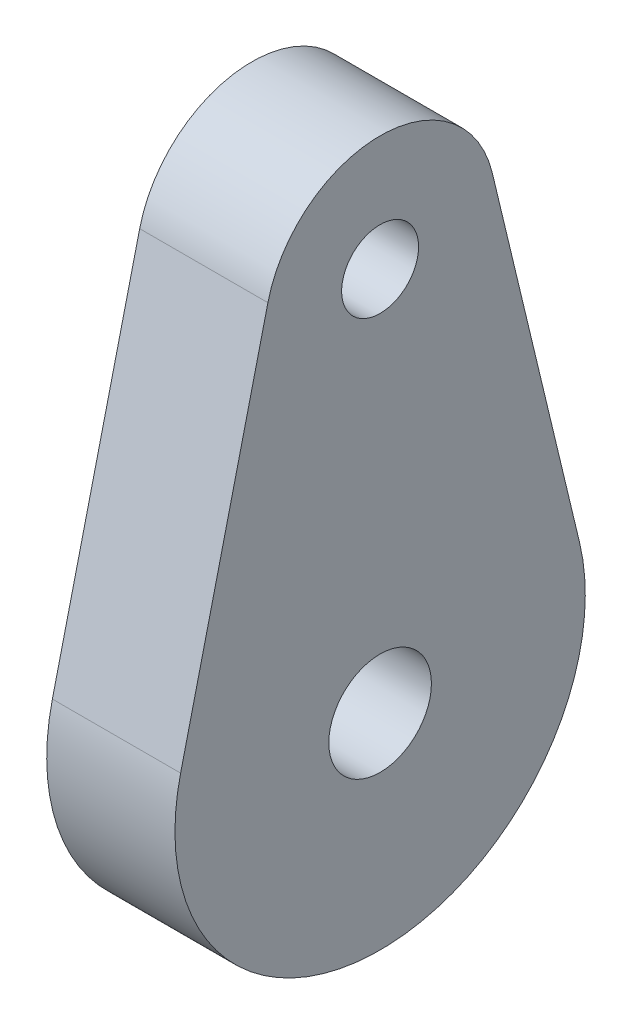
SolidWorks part; units mm, degrees
ref_plane "前视基准面" through (0, 0, 0) normal (0, 0, 1) x (1, 0, 0)
ref_plane "上视基准面" through (0, 0, 0) normal (0, 1, 0) x (1, 0, 0)
ref_plane "右视基准面" through (0, 0, 0) normal (1, 0, 0) x (0, 0, -1)
sketch "草图1" plane through (0, 0, 0) normal (1, 0, 0) x (0, 0, -1)
  line L0 (-7.7792, 1.8667) -> (-4.3758, 16.05)
  line L1 (0, 15) -> (0, 0) construction
  line L2 (4.3758, 16.05) -> (7.7792, 1.8667)
  arc A0 (4.3758, 16.05) -> (-4.3758, 16.05) centre (0, 15) ccw
  circle A1 centre (0, 0) radius 2
  arc A2 (-7.7792, 1.8667) -> (7.7792, 1.8667) centre (0, 0) ccw
  circle A3 centre (0, 15) radius 1.5
  dimension "D1" = 3
  dimension "D2" = 4
  dimension "D3" = 9
  dimension "D5" = 16
  dimension "D4" = 15
extrude "凸台-拉伸1" add sketch "草图1" along normal blind 5
sketch "草图2" plane through (0, 0, 0) normal (-1, 0, 0) x (0, 0, 1)
  circle A0 centre (0, 0) radius 3
  circle A1 centre (0, 0) radius 2 construction
  circle A2 centre (0, 0) radius 2
  dimension "D1" = 6
extrude "凸台-拉伸2" add sketch "草图2" along normal blind 0.5
